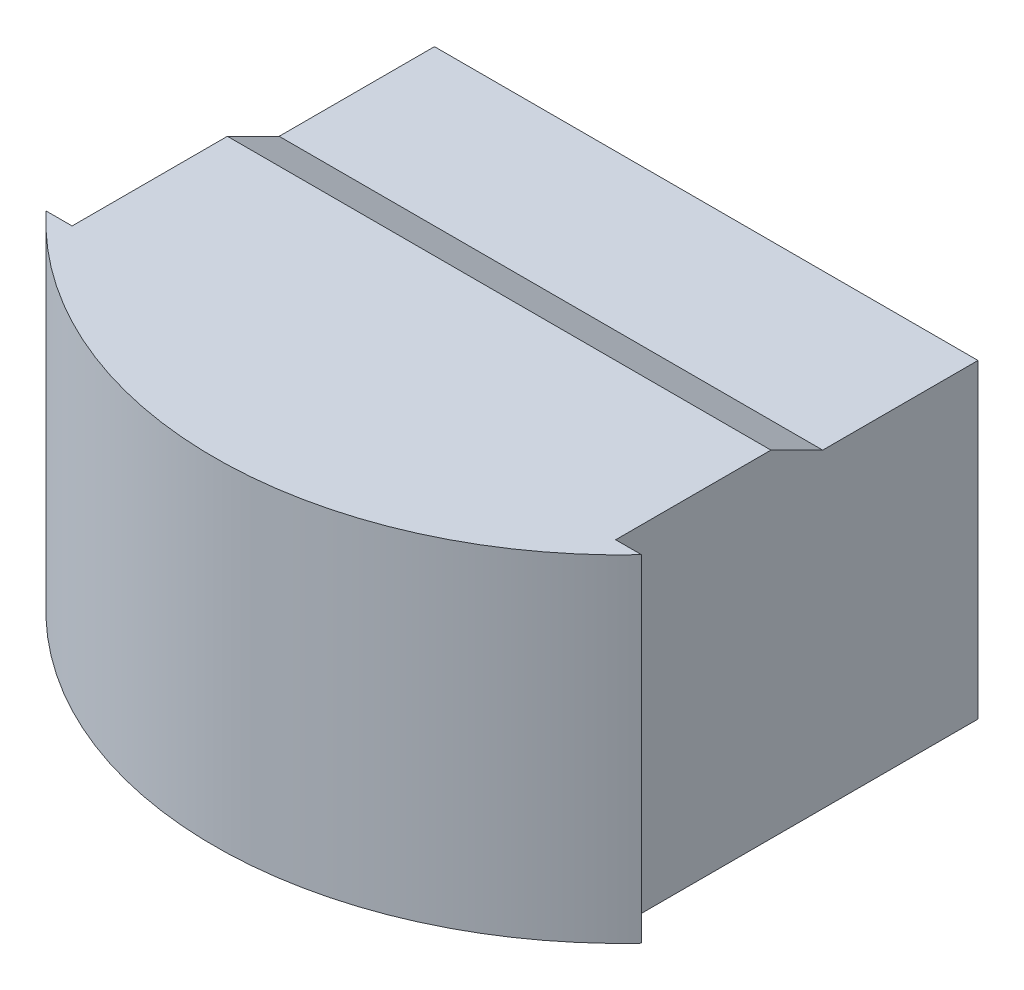
SolidWorks part; units mm, degrees
ref_plane "Front Plane" through (0, 0, 0) normal (0, 0, 1) x (1, 0, 0)
ref_plane "Top Plane" through (0, 0, 0) normal (0, 1, 0) x (1, 0, 0)
ref_plane "Right Plane" through (0, 0, 0) normal (1, 0, 0) x (0, 0, -1)
sketch "Sketch4" plane through (0, 0, 0) normal (0, 1, 0) x (1, 0, 0)
  line L0 (-6.35, 0) -> (139.7, 0)
  line L1 (0, 0) -> (133.35, 0)
  line L2 (0, 0) -> (0, 88.9)
  line L3 (0, 88.9) -> (133.35, 88.9)
  line L4 (133.35, 0) -> (133.35, 88.9)
  arc A1 (-6.35, 0) -> (139.7, 0) centre (66.675, 68.1037) ccw
  point P6 (66.675, -31.75)
  point P9 (66.675, 0)
  dimension "D1" = 133.35
  dimension "D2" = 88.9
  dimension "D3" = 146.05
  dimension "D4" = 6.35
  dimension "D5" = 31.75
extrude "Boss-Extrude2" add sketch "Sketch4" along normal blind 82.55 contours L0 A1 | L0 L4 L3 L2 region at (66.675, 0, 12.8907) region at (66.675, 0, -44.45)
sketch "Sketch5" plane through (0, 0, 0) normal (1, 0, 0) x (0, 0, -1)
  line L0 (0, 82.55) -> (88.9, 82.55) construction
  line L1 (0, 82.55) -> (88.9, 82.55)
  line L2 (88.9, 82.55) -> (88.9, 76.2)
  line L3 (88.9, 82.55) -> (88.9, 0) construction
  line L4 (88.9, 76.2) -> (50.8, 76.2)
  line L5 (50.8, 76.2) -> (38.1, 82.55)
  line L6 (38.1, 82.55) -> (88.9, 82.55)
  dimension "D1" = 12.7
  dimension "D2" = 38.1
  dimension "D3" = 6.35
extrude "Cut-Extrude4" cut sketch "Sketch5" along normal through all contours L2 L4 L5 L6
